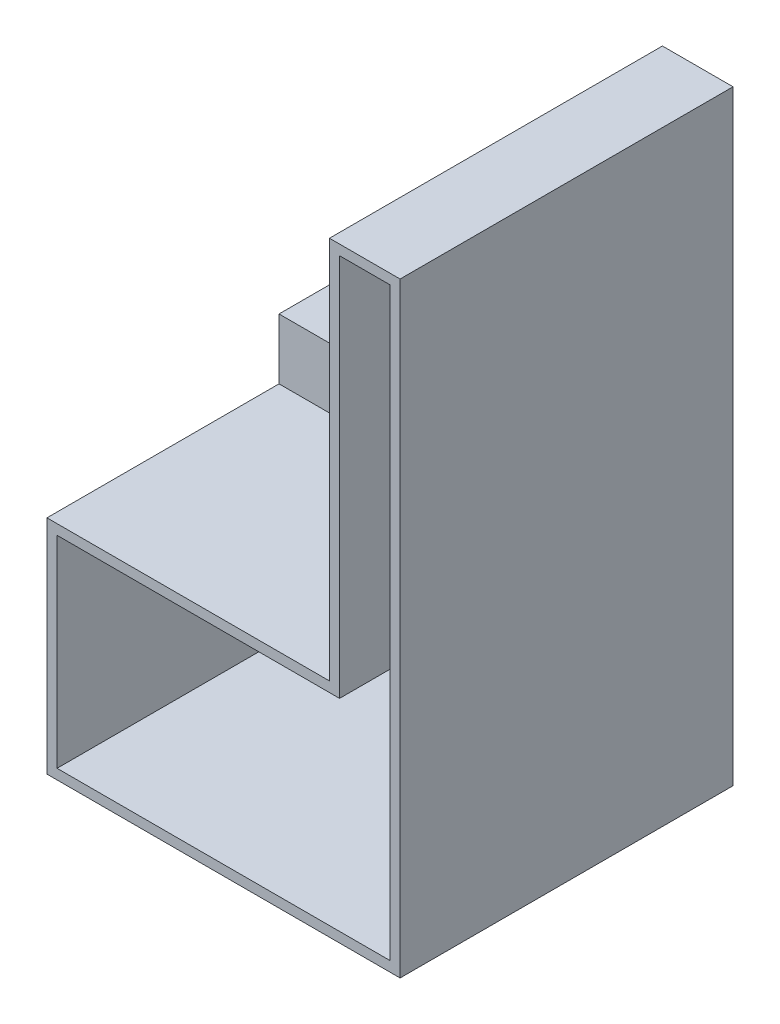
SolidWorks part; units mm, degrees
ref_plane "正面" through (0, 0, 0) normal (0, 0, 1) x (1, 0, 0)
ref_plane "平面" through (0, 0, 0) normal (0, 1, 0) x (1, 0, 0)
ref_plane "右側面" through (0, 0, 0) normal (1, 0, 0) x (0, 0, -1)
sketch "ｽｹｯﾁ2" plane through (0, 0, 0) normal (0, 0, 1) x (1, 0, 0)
  line L0 (0, 0) -> (0, 160)
  line L1 (0, 160) -> (35, 160)
  line L2 (35, 160) -> (35, -140)
  line L3 (35, -140) -> (-140, -140)
  line L4 (-140, -140) -> (-140, 0)
  line L5 (-140, 0) -> (0, 0)
  dimension "D1" = 140
  dimension "D2" = 175
  dimension "D3" = 35
  dimension "D4" = 300
extrude "ﾎﾞｽ - 押し出し1" add sketch "ｽｹｯﾁ2" along normal blind 50
sketch "ｽｹｯﾁ3" plane through (0, 0, 50) normal (0, 0, 1) x (1, 0, 0)
  line L0 (-140, -30) -> (-140, -140)
  line L1 (-140, 0) -> (-140, -140) construction
  line L2 (-140, -140) -> (35, -140)
  line L3 (35, -140) -> (35, 160)
  line L4 (35, 160) -> (0, 160)
  line L5 (0, 160) -> (0, -30)
  line L6 (0, -30) -> (-140, -30)
  dimension "D1" = 110
extrude "ﾎﾞｽ - 押し出し2" add sketch "ｽｹｯﾁ3" along normal blind 115
shell "ｼｪﾙ1" thickness 5 removed face at (-35, -3.3333, 165)
